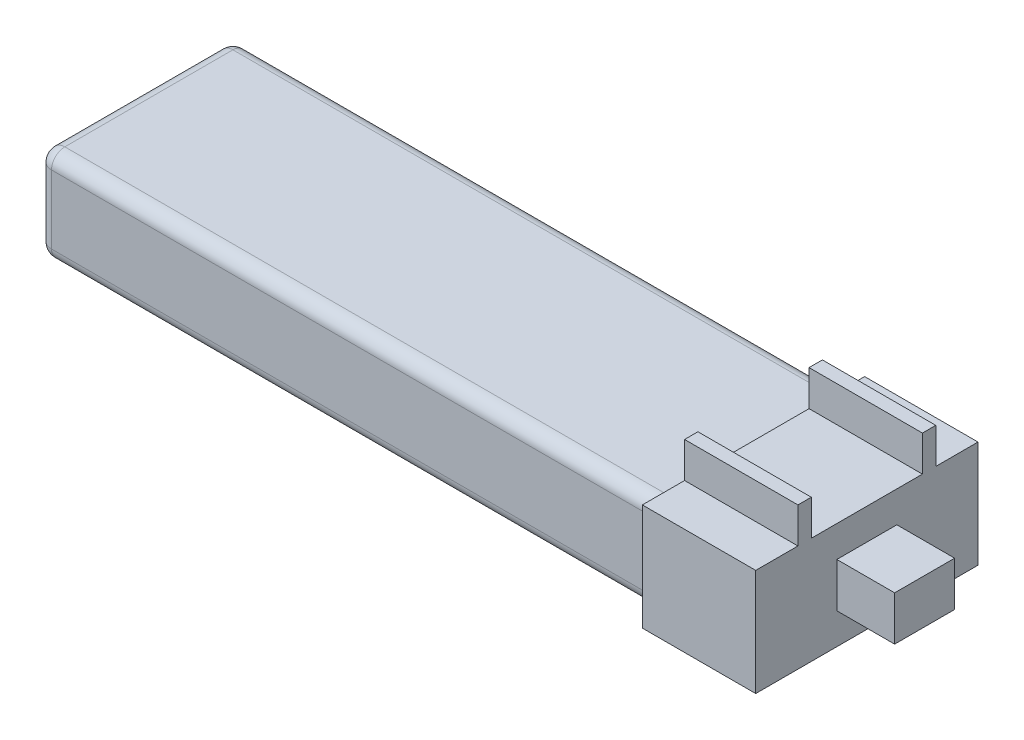
SolidWorks part; units mm, degrees
ref_plane "Front Plane" through (0, 0, 0) normal (0, 0, 1) x (1, 0, 0)
ref_plane "Top Plane" through (0, 0, 0) normal (0, 1, 0) x (1, 0, 0)
ref_plane "Right Plane" through (0, 0, 0) normal (1, 0, 0) x (0, 0, -1)
sketch "Sketch1" plane through (0, 0, 0) normal (0, 1, 0) x (1, 0, 0)
  line L1 (-20.955, -6.35) -> (20.955, -6.35)
  line L2 (-20.955, -6.35) -> (-20.955, 6.35)
  line L3 (-20.955, 6.35) -> (20.955, 6.35)
  line L4 (20.955, -6.35) -> (20.955, 6.35)
  line L5 (-20.955, -6.35) -> (20.955, 6.35) construction
  line L6 (-20.955, 6.35) -> (20.955, -6.35) construction
  point P0 (0, 0)
  dimension "D1" = 41.91
  dimension "D2" = 12.7
extrude "Boss-Extrude1" add sketch "Sketch1" along normal mid plane 6.096
sketch "Sketch2" plane through (20.955, 0, 0) normal (1, 0, 0) x (0, 0, -1)
  line L0 (-3.937, 0) -> (3.937, 0)
  line L1 (-3.937, 0) -> (-3.937, 5.08)
  line L2 (-3.937, 5.08) -> (-3.175, 5.08)
  line L3 (-3.175, 5.08) -> (-3.175, 0)
  line L4 (-6.35, 3.048) -> (6.35, 3.048) construction
  line L5 (0, 0) -> (0, 6.5508) construction
  line L6 (3.937, 0) -> (3.937, 5.08)
  line L7 (3.175, 5.08) -> (3.175, 0)
  line L8 (3.937, 5.08) -> (3.175, 5.08)
  line L10 (-1.7145, -1.27) -> (1.7145, -1.27)
  line L11 (-1.7145, -1.27) -> (-1.7145, 1.27)
  line L12 (-1.7145, 1.27) -> (1.7145, 1.27)
  line L13 (1.7145, -1.27) -> (1.7145, 1.27)
  line L14 (-1.7145, -1.27) -> (1.7145, 1.27) construction
  line L15 (-1.7145, 1.27) -> (1.7145, -1.27) construction
  point P4 (0, 0)
  line M8 (6.35, 3.048) -> (-6.35, 3.048)
  dimension "D1" = 3.175
  dimension "D2" = 0.762
  dimension "D3" = 2.032
  dimension "D4" = 2.54
  dimension "D5" = 3.429
extrude "Boss-Extrude2" add sketch "Sketch2" against normal blind 6.604 contours L3 L2 L1 M8 | L6 L8 L7 M8 region at (20.955, 4.064, 3.556) region at (20.955, 4.064, -3.556)
extrude "Boss-Extrude3" add sketch "Sketch2<3>" along normal blind 3.175 contours L0 L13 L12 L11 | L10 L13 L0 L11 region at (20.955, 0.635, 0) region at (20.955, -0.635, 0)
sketch "Sketch2<3>" plane through (20.955, 0, 0) normal (1, 0, 0) x (0, 0, -1) same geometry as "Sketch2"
sketch "Sketch4" plane through (20.955, 0, 0) normal (1, 0, 0) x (0, 0, -1)
  line L1 (-5.5626, -2.7178) -> (5.5626, -2.7178)
  line L2 (-5.5626, -2.7178) -> (-5.5626, 2.7178)
  line L3 (-5.5626, 2.7178) -> (5.5626, 2.7178)
  line L4 (5.5626, -2.7178) -> (5.5626, 2.7178)
  line L5 (-5.5626, -2.7178) -> (5.5626, 2.7178) construction
  line L6 (-5.5626, 2.7178) -> (5.5626, -2.7178) construction
  line L7 (-7.12, -3.9586) -> (7.12, -3.9586)
  line L8 (-7.12, -3.9586) -> (-7.12, 3.9586)
  line L9 (-7.12, 3.9586) -> (7.12, 3.9586)
  line L10 (7.12, -3.9586) -> (7.12, 3.9586)
  line L11 (-7.12, -3.9586) -> (7.12, 3.9586) construction
  line L12 (-7.12, 3.9586) -> (7.12, -3.9586) construction
  point P0 (0, 0)
  point P5 (0, 0)
  dimension "D1" = 5.4356
  dimension "D2" = 11.1252
extrude "Cut-Extrude1" cut sketch "Sketch4" against normal through all from surface starting at face at (14.351, 4.064, -3.556)
fillet "Fillet1" radius 0.762 8 edges at (-20.955, 0, 5.5626) (-20.955, 0, -5.5626) (-3.302, -2.7178, -5.5626) (-3.302, -2.7178, 5.5626) (-20.955, -2.7178, 0) (-20.955, 2.7178, 0) (-3.302, 2.7178, -5.5626) (-3.302, 2.7178, 5.5626)
sketch "Sketch5" plane through (20.955, 0, 0) normal (1, 0, 0) x (0, 0, -1)
  line L12 (-6.35, -3.048) -> (6.35, -3.048)
  line L13 (6.35, -3.048) -> (6.35, 3.048)
  line L14 (6.35, 3.048) -> (3.937, 3.048)
  line L15 (3.937, 3.048) -> (3.937, 5.08)
  line L16 (3.937, 5.08) -> (3.175, 5.08)
  line L17 (3.175, 5.08) -> (3.175, 3.048)
  line L18 (3.175, 3.048) -> (-3.175, 3.048)
  line L19 (-3.175, 3.048) -> (-3.175, 5.08)
  line L20 (-3.175, 5.08) -> (-3.937, 5.08)
  line L21 (-3.937, 5.08) -> (-3.937, 3.048)
  line L22 (-3.937, 3.048) -> (-6.35, 3.048)
  line L23 (-6.35, 3.048) -> (-6.35, -3.048)
  line L24 (-6.35, -3.048) -> (6.35, -3.048)
  line L25 (6.35, -3.048) -> (6.35, 3.048)
  line L26 (6.35, 3.048) -> (3.937, 3.048)
  line L27 (3.937, 3.048) -> (3.937, 5.08)
  line L28 (3.937, 5.08) -> (3.175, 5.08)
  line L29 (3.175, 5.08) -> (3.175, 3.048)
  line L30 (3.175, 3.048) -> (-3.175, 3.048)
  line L31 (-3.175, 3.048) -> (-3.175, 5.08)
  line L32 (-3.175, 5.08) -> (-3.937, 5.08)
  line L33 (-3.937, 5.08) -> (-3.937, 3.048)
  line L34 (-3.937, 3.048) -> (-6.35, 3.048)
  line L35 (-6.35, 3.048) -> (-6.35, -3.048)
  dimension "D1" = 0
extrude "Cut-Extrude2" cut sketch "Sketch5" against normal blind 0.127
sketch "Sketch6" plane through (20.955, 0, 0) normal (-1, 0, 0) x (0, 0, 1)
  line L4 (1.7145, -1.27) -> (1.7145, 1.27)
  line L5 (1.7145, 1.27) -> (-1.7145, 1.27)
  line L6 (-1.7145, 1.27) -> (-1.7145, -1.27)
  line L7 (-1.7145, -1.27) -> (1.7145, -1.27)
  line L8 (1.7145, -1.27) -> (1.7145, 1.27)
  line L9 (1.7145, 1.27) -> (-1.7145, 1.27)
  line L10 (-1.7145, 1.27) -> (-1.7145, -1.27)
  line L11 (-1.7145, -1.27) -> (1.7145, -1.27)
  dimension "D1" = 0
extrude "Boss-Extrude4" add sketch "Sketch6" along normal up to surface (0.127 mm away) up to face at (20.828, 2.7093, 0)
